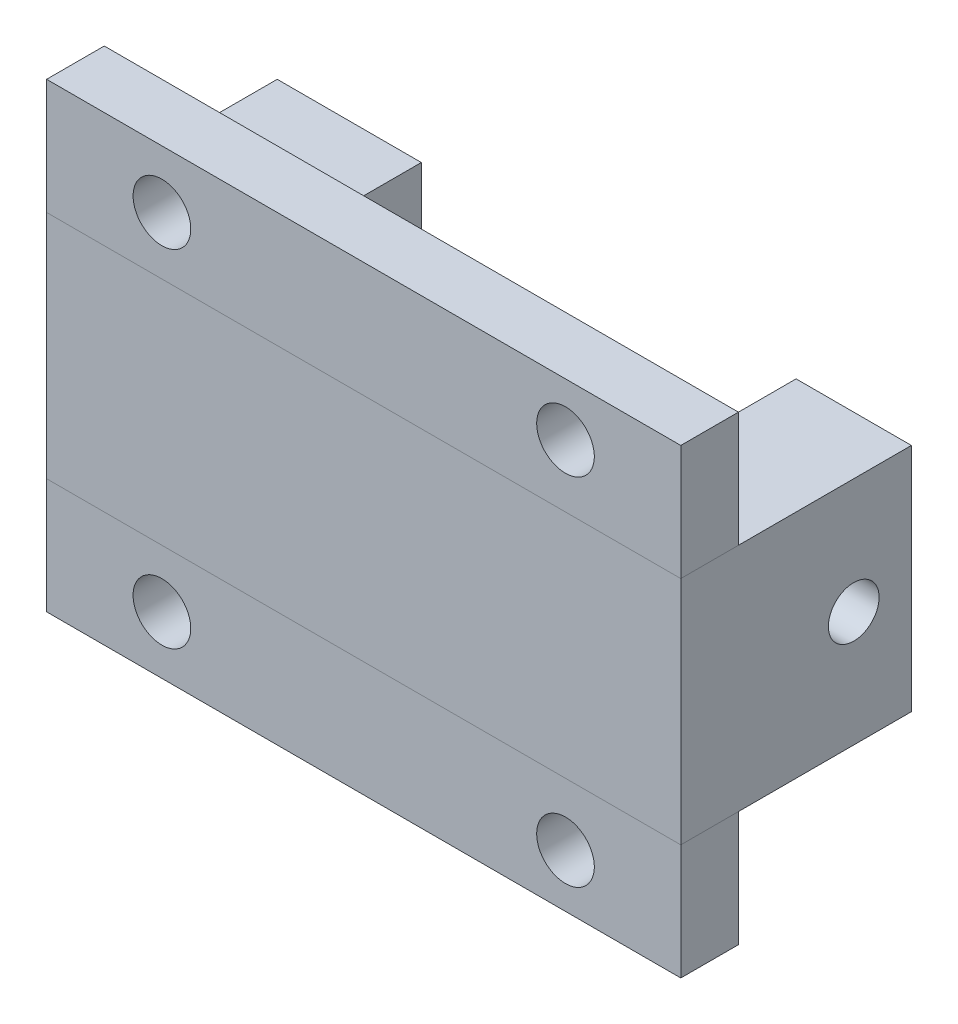
SolidWorks part; units mm, degrees
note: '?' marks a value the reader was unsure of.
material "炭素鋼(普通)"
ref_plane "VERT" through (0, 0, 0) normal (0, 0, 1) x (1, 0, 0)
ref_plane "HOR" through (0, 0, 0) normal (0, 1, 0) x (1, 0, 0)
ref_plane "CTR" through (0, 0, 0) normal (1, 0, 0) x (0, 0, -1)
ref_axis "A_X" through (115.5, 0, 0) along (-1, 0, 0)?
ref_axis "A_Y" through (0, 44, 0) along (0, -1, 0)?
ref_axis "A_Z" through (0, 0, 2) along (0, 0, -1)?
sketch3d "PNT_CG"
  point P0 (0, 0, 0)
sketch "Sketch3" plane through (0, 0, 0) normal (0, 1, 0) x (1, 0, 0)
  line L1 (0, 0) -> (110, 0)
  line L2 (0, 0) -> (0, 40)
  line L3 (0, 40) -> (110, 40)
  line L4 (110, 0) -> (110, 40)
  dimension "D1" = 40
  dimension "D2" = 110
extrude "Boss-Extrude2" add sketch "Sketch3" along normal mid plane 40
sketch "Sketch4" plane through (0, 0, 0) normal (0, 1, 0) x (1, 0, 0)
  line L0 (25, 50.3852) -> (25, 20)
  line L1 (25, 20) -> (90, 20)
  line L2 (90, 20) -> (90, 48.5379)
  line L3 (0, -22) -> (0, 22) construction
  line L4 (110, 40) -> (0, 40) construction
  dimension "D1" = 25
  dimension "D2" = 20
  dimension "D3" = 65
split "Split2" trim tools "Sketch4" bodies to split 103 resulting bodies 104
ref_plane "Plane1" through (110, 20, 0) normal (1, 0, 0) x (0, 0, -1)
sketch "Sketch5" plane through (110, 20, 0) normal (1, 0, 0) x (0, 0, -1)
  line L0 (0, 0) -> (40, 0)
  line L1 (0, 0) -> (40, 0)
sketch "Sketch6" plane through (0, 20, 0) normal (0, 1, 0) x (1, 0, 0)
  line L1 (0, 0) -> (110, 0)
  line L2 (0, 0) -> (0, 10)
  line L3 (0, 10) -> (110, 10)
  line L4 (110, 0) -> (110, 10)
  line L8 (90, 20) -> (25, 20)
  line L9 (25, 20) -> (25, 40)
  line L10 (25, 40) -> (0, 40)
  line L11 (0, 40) -> (0, 0)
  line L12 (0, 0) -> (110, 0)
  line L13 (110, 0) -> (110, 40)
  line L14 (110, 40) -> (90, 40)
  line L15 (90, 40) -> (90, 20)
  line L16 (90, 20) -> (25, 20)
  line L17 (25, 20) -> (25, 40)
  line L18 (25, 40) -> (0, 40)
  line L19 (0, 40) -> (0, 0)
  line L20 (0, 0) -> (110, 0)
  line L21 (110, 0) -> (110, 40)
  line L22 (110, 40) -> (90, 40)
  line L23 (90, 40) -> (90, 20)
  line M13 (0, 40) -> (0, 0)
  line M14 (0, 0) -> (110, 0)
  line M15 (110, 0) -> (110, 40)
  dimension "D2" = 10
  dimension "D1" = 0
extrude "Boss-Extrude3" add sketch "Sketch6" along normal blind 20 separate body contours L3 M13 M14 M15
sketch "Sketch7" plane through (0, 0, -10) normal (0, 0, -1) x (-1, 0, 0)
  line L0 (0, 22) -> (0, -22) construction
  line L2 (0, 40) -> (-110, 40) construction
  line L3 (-110, 50.25) -> (-110, -10.25) construction
  point P0 (-20, 30)
  point P1 (-90, 30.8146)
  dimension "D1" = 20
  dimension "D2" = 10
  dimension "D3" = 20
hole_wizard "M8 Clearance Hole1" positions "Sketch8" profile "Sketch9" hole size "M8" standard "JIS" end condition through all
sketch "Sketch8" plane through (0, 0, -10) normal (0, 0, -1) x (-1, 0, 0)
  point P0 (-20, 30)
  point P3 (-90, 30.8146)
sketch "Sketch9" plane through (20, 30, -10) normal (1, 0, 0) x (0, 1, 0)
  line L0 (0, 0) -> (0, 10)
  line L1 (0, 10) -> (5, 10)
  line L2 (5, 10) -> (5, 0)
  line L5 (5, 0) -> (0, 0)
  line L11 (0, -6.35) -> (0, 107.95) construction
  dimension "Thru Hole Dia." = 10
  dimension "Thru Hole Depth" = 10
mirror "Mirror1" about plane through (0, 0, 0) normal (0, 1, 0) of bodies 106
sketch "Sketch10" plane through (0, 0, -20) normal (0, 0, -1) x (-1, 0, 0)
  line L0 (-25, -10) -> (-90, -10)
  line L1 (-25, 20) -> (-25, -20) construction
  line L2 (-90, -20) -> (-90, 20) construction
  line L3 (-25, 10) -> (-90, 10)
  line L6 (-25, 44) -> (-25, -44) construction
  line L8 (-18.7583, 0) -> (-102.9524, 0) construction
  line L9 (22, 0) -> (-22, 0) construction
  line L10 (36.1499, 0) -> (-248.1662, 0) construction
  line L11 (-25, -10) -> (-25, 10)
  line L12 (-90, -10) -> (-90, 10)
  dimension "D1" = 10
extrude "Cut-Extrude1" cut sketch "Sketch10" against normal blind 7 contours L3 L12 L0 L11
fillet "Fillet1" radius 5 4 edges at (90, 10, -16.5) (90, -10, -16.5) (25, 10, -16.5) (25, -10, -16.5)
sketch "Sketch13" plane through (110, 0, 0) normal (1, 0, 0) x (0, 0, -1)
  point P0 (30, 0)
  point P1 (0, 0)
  point P3 (0, 0)
  point P4 (0, 0)
hole_wizard "M10x1.25 Tapped Hole1" positions "Sketch14" profile "Sketch15" tap size "M10x1.25" standard "JIS" end condition up to next
sketch "Sketch14" plane through (110, 0, 0) normal (1, 0, 0) x (0, 0, -1)
  point P0 (30, 0)
sketch "Sketch15" plane through (110, 0, -30) normal (0, 1, 0) x (0, 0, -1)
  line L0 (0, 0) -> (0, 20.001)
  line L1 (0, 20.001) -> (4.4, 20.001)
  line L2 (4.4, 20.001) -> (4.4, 0)
  line L5 (4.4, 0) -> (0, 0)
  line L11 (0, -6.35) -> (0, 107.95) construction
  dimension "Thru Tap Drill Dia." = 8.8
  dimension "Thru Tap Drill Depth" = 20.001
cosmetic thread "Hole Thread1" parameters "D2"=10
